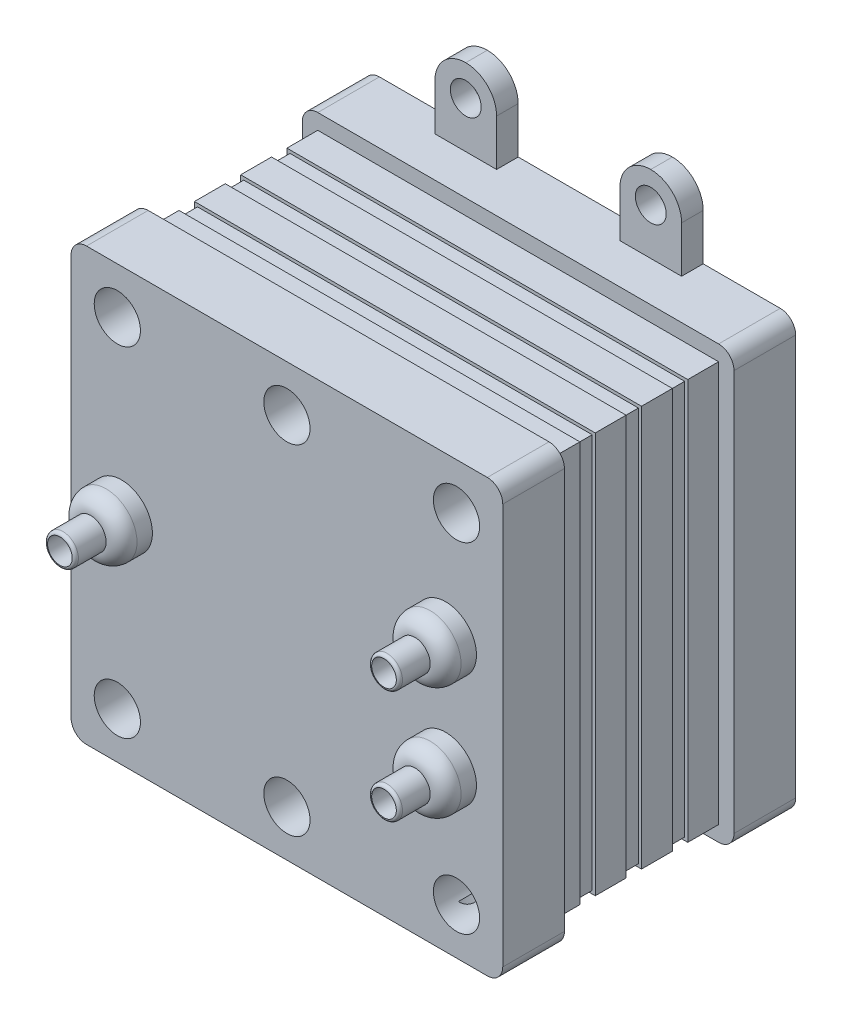
SolidWorks part; units mm, degrees
ref_plane "Plan de face" through (0, 0, 0) normal (0, 0, 1) x (1, 0, 0)
ref_plane "Plan de dessus" through (0, 0, 0) normal (0, 1, 0) x (1, 0, 0)
ref_plane "Plan de droite" through (0, 0, 0) normal (1, 0, 0) x (0, 0, -1)
sketch "Esquisse1" plane through (0, 0, 0) normal (0, 0, 1) x (1, 0, 0)
  line L1 (-74.4634, 41.4286) -> (55.5366, 41.4286)
  line L2 (-79.4634, 36.4286) -> (-79.4634, -93.5714)
  line L3 (-74.4634, -98.5714) -> (55.5366, -98.5714)
  line L4 (60.5366, 36.4286) -> (60.5366, -93.5714)
  arc A0 (-74.4634, 41.4286) -> (-79.4634, 36.4286) centre (-74.4634, 36.4286) ccw
  arc A1 (55.5366, 41.4286) -> (60.5366, 36.4286) centre (55.5366, 36.4286) cw
  arc A2 (55.5366, -98.5714) -> (60.5366, -93.5714) centre (55.5366, -93.5714) ccw
  arc A3 (-79.4634, -93.5714) -> (-74.4634, -98.5714) centre (-74.4634, -93.5714) ccw
  point P6 (-79.4634, 41.4286)
  point P9 (60.5366, 41.4286)
  point P14 (-79.4634, -98.5714)
  dimension "D3" = 5
  dimension "D1" = 140
  dimension "D2" = 140
extrude "Boss.-Extru.1" add sketch "Esquisse1" along normal blind 20
sketch "Esquisse2" plane through (0, 0, 20) normal (0, 0, 1) x (1, 0, 0)
  line L0 (-79.4634, 36.4286) -> (-79.4634, -93.5714) construction
  line L1 (-74.4634, 36.4286) -> (55.5366, 36.4286)
  line L2 (-74.4634, 36.4286) -> (-74.4634, -93.5714)
  line L3 (-74.4634, -93.5714) -> (55.5366, -93.5714)
  line L4 (55.5366, 36.4286) -> (55.5366, -93.5714)
  line L5 (60.5366, -93.5714) -> (60.5366, 36.4286) construction
  line L6 (-74.4634, -98.5714) -> (55.5366, -98.5714) construction
  line L7 (55.5366, 41.4286) -> (-74.4634, 41.4286) construction
  dimension "D1" = 5
  dimension "D2" = 5
  dimension "D3" = 5
  dimension "D4" = 5
extrude "Boss.-Extru.2" add sketch "Esquisse2" along normal blind 10
sketch "Esquisse4" plane through (0, 0, 30) normal (0, 0, 1) x (1, 0, 0)
  line L0 (55.5366, 36.4286) -> (-74.4634, 36.4286) construction
  line L1 (-73.4634, 35.4286) -> (54.5366, 35.4286)
  line L2 (-73.4634, 35.4286) -> (-73.4634, -92.5714)
  line L3 (-73.4634, -92.5714) -> (54.5366, -92.5714)
  line L4 (54.5366, 35.4286) -> (54.5366, -92.5714)
  line L5 (-74.4634, -93.5714) -> (55.5366, -93.5714) construction
  line L6 (-74.4634, 36.4286) -> (-74.4634, -93.5714) construction
  line L7 (55.5366, -93.5714) -> (55.5366, 36.4286) construction
  dimension "D1" = 1
  dimension "D2" = 1
  dimension "D3" = 1
  dimension "D4" = 1
extrude "Boss.-Extru.4" add sketch "Esquisse4" along normal blind 5
sketch "Esquisse5" plane through (0, 0, 35) normal (0, 0, 1) x (1, 0, 0)
  line L1 (-74.4634, 36.4286) -> (55.5366, 36.4286)
  line L2 (-74.4634, 36.4286) -> (-74.4634, -93.5714)
  line L3 (-74.4634, -93.5714) -> (55.5366, -93.5714)
  line L4 (55.5366, 36.4286) -> (55.5366, -93.5714)
extrude "Boss.-Extru.5" add sketch "Esquisse5" along normal blind 10
sketch "Esquisse6" plane through (0, 0, 45) normal (0, 0, 1) x (1, 0, 0)
  line L0 (-74.4634, 36.4286) -> (-74.4634, -93.5714) construction
  line L1 (-73.4634, 35.4286) -> (54.5366, 35.4286)
  line L2 (-73.4634, 35.4286) -> (-73.4634, -92.5714)
  line L3 (-73.4634, -92.5714) -> (54.5366, -92.5714)
  line L4 (54.5366, 35.4286) -> (54.5366, -92.5714)
  line L5 (55.5366, 36.4286) -> (-74.4634, 36.4286) construction
  line L6 (-74.4634, -93.5714) -> (55.5366, -93.5714) construction
  line L7 (55.5366, -93.5714) -> (55.5366, 36.4286) construction
  dimension "D1" = 1
  dimension "D2" = 1
  dimension "D3" = 1
  dimension "D4" = 1
extrude "Boss.-Extru.6" add sketch "Esquisse6" along normal blind 5
sketch "Esquisse7" plane through (0, 0, 50) normal (0, 0, 1) x (1, 0, 0)
  line L1 (-74.4634, 36.4286) -> (55.5366, 36.4286)
  line L2 (-74.4634, 36.4286) -> (-74.4634, -93.5714)
  line L3 (-74.4634, -93.5714) -> (55.5366, -93.5714)
  line L4 (55.5366, 36.4286) -> (55.5366, -93.5714)
extrude "Boss.-Extru.7" add sketch "Esquisse7" along normal blind 10
sketch "Esquisse8" plane through (0, 0, 60) normal (0, 0, 1) x (1, 0, 0)
  line L0 (-74.4634, 36.4286) -> (-74.4634, -93.5714) construction
  line L1 (-73.4634, 35.4286) -> (54.5366, 35.4286)
  line L2 (-73.4634, 35.4286) -> (-73.4634, -92.5714)
  line L3 (-73.4634, -92.5714) -> (54.5366, -92.5714)
  line L4 (54.5366, 35.4286) -> (54.5366, -92.5714)
  line L5 (55.5366, 36.4286) -> (-74.4634, 36.4286) construction
  line L6 (55.5366, -93.5714) -> (55.5366, 36.4286) construction
  line L7 (-74.4634, -93.5714) -> (55.5366, -93.5714) construction
  dimension "D1" = 1
  dimension "D2" = 1
  dimension "D3" = 1
  dimension "D4" = 1
extrude "Boss.-Extru.8" add sketch "Esquisse8" along normal blind 5
sketch "Esquisse9" plane through (0, 0, 65) normal (0, 0, 1) x (1, 0, 0)
  line L1 (-74.4634, 36.4286) -> (55.5366, 36.4286)
  line L2 (-74.4634, 36.4286) -> (-74.4634, -93.5714)
  line L3 (-74.4634, -93.5714) -> (55.5366, -93.5714)
  line L4 (55.5366, 36.4286) -> (55.5366, -93.5714)
extrude "Boss.-Extru.9" add sketch "Esquisse9" along normal blind 10
sketch "Esquisse10" plane through (0, 0, 75) normal (0, 0, 1) x (1, 0, 0)
  line L0 (-74.4634, -98.5714) -> (55.5366, -98.5714) construction
  line L1 (55.5366, -98.5714) -> (-74.4634, -98.5714)
  line L2 (60.5366, -93.5714) -> (60.5366, 36.4286)
  line L3 (55.5366, 41.4286) -> (-74.4634, 41.4286)
  line L4 (-79.4634, -93.5714) -> (-79.4634, 36.4286)
  line L5 (-79.4634, 36.4286) -> (-79.4634, -93.5714) construction
  arc A0 (-74.4634, -98.5714) -> (-79.4634, -93.5714) centre (-74.4634, -93.5714) cw
  arc A1 (55.5366, -98.5714) -> (60.5366, -93.5714) centre (55.5366, -93.5714) ccw
  arc A2 (60.5366, 36.4286) -> (55.5366, 41.4286) centre (55.5366, 36.4286) ccw
  arc A3 (-74.4634, 41.4286) -> (-79.4634, 36.4286) centre (-74.4634, 36.4286) ccw
  point P10 (-79.4634, -98.5714)
  point P13 (60.5366, -98.5714)
  point P18 (-79.4634, 41.4286)
  dimension "D3" = 5
  dimension "D1" = 140
  dimension "D2" = 140
extrude "Boss.-Extru.10" add sketch "Esquisse10" along normal blind 20
sketch "Esquisse11" plane through (0, 0, 0) normal (0, 0, -1) x (-1, 0, 0)
  line L0 (-60.5366, -93.5714) -> (-60.5366, 36.4286) construction
  line L1 (-55.5366, 41.4286) -> (74.4634, 41.4286) construction
  line L2 (79.4634, 36.4286) -> (79.4634, -93.5714) construction
  line L3 (74.4634, -98.5714) -> (-55.5366, -98.5714) construction
  circle A0 centre (-45.5366, 26.4286) radius 7.5
  circle A1 centre (9.4634, 26.4286) radius 7.5
  circle A2 centre (64.4634, 26.4286) radius 7.5
  circle A3 centre (64.4634, -83.5714) radius 7.5
  circle A4 centre (9.4634, -83.5714) radius 7.5
  circle A5 centre (-45.5366, -83.5714) radius 7.5
  dimension "D13" = 15
  dimension "D1" = 15
  dimension "D2" = 15
  dimension "D3" = 15
  dimension "D4" = 15
  dimension "D5" = 55
  dimension "D6" = 15
  dimension "D7" = 15
  dimension "D8" = 15
  dimension "D9" = 15
  dimension "D10" = 15
  dimension "D11" = 15
  dimension "D12" = 55
extrude "Enlèv. mat.-Extru.1" cut sketch "Esquisse11" against normal blind 110
sketch "Esquisse12" plane through (0, 0, 95) normal (0, 0, 1) x (1, 0, 0)
  circle A0 centre (42.0179, -10.2314) radius 10
  circle A1 centre (42.0179, -46.8914) radius 10
  circle A2 centre (-63.0897, -28.5714) radius 10
  circle A3 centre (45.5366, 26.4286) radius 7.5 construction
  circle A4 centre (45.5366, -83.5714) radius 7.5 construction
  circle A5 centre (-64.4634, 26.4286) radius 7.5 construction
  dimension "D5" = 20
  dimension "D1" = 36.66
  dimension "D2" = 36.66
  dimension "D3" = 36.68
  dimension "D4" = 55
extrude "Boss.-Extru.11" add sketch "Esquisse12" along normal blind 10
sketch "Esquisse13" plane through (0, 0, 105) normal (0, 0, 1) x (1, 0, 0)
  circle A0 centre (42.0179, -10.2314) radius 5
  circle A1 centre (42.0179, -46.8914) radius 5
  circle A2 centre (-63.0897, -28.5714) radius 5
  dimension "D1" = 10
  dimension "D2" = 10
  dimension "D3" = 10
extrude "Boss.-Extru.12" add sketch "Esquisse13" along normal blind 10
fillet "Congé2" radius 5 1 edges at (-53.0897, -28.5714, 105)
fillet "Congé3" radius 5 2 edges at (52.0179, -46.8914, 105) (52.0179, -10.2314, 105)
sketch "Esquisse14" plane through (0, 0, 115) normal (0, 0, 1) x (1, 0, 0)
  circle A0 centre (42.0179, -10.2314) radius 4
  circle A1 centre (42.0179, -46.8914) radius 4
  circle A2 centre (-63.0897, -28.5714) radius 4
  dimension "D1" = 8
  dimension "D2" = 8
  dimension "D3" = 8
extrude "Enlèv. mat.-Extru.2" cut sketch "Esquisse14" against normal blind 10
fillet "Congé4" radius 1 3 edges at (47.0179, -46.8914, 115) (47.0179, -10.2314, 115) (-58.0897, -28.5714, 115)
sketch "Esquisse15" plane through (0, -98.5714, 0) normal (0, -1, 0) x (1, 0, 0)
  circle A0 centre (-53.5135, 9.4224) radius 5
  circle A1 centre (36.4865, 9.4224) radius 5
  circle A2 centre (36.4865, 85.1887) radius 5
  circle A3 centre (-53.5135, 85.1887) radius 5
  dimension "D1" = 10
  dimension "D2" = 90
  dimension "D3" = 90
extrude "Enlèv. mat.-Extru.3" cut sketch "Esquisse15" against normal blind 10
sketch "Esquisse16" plane through (0, 41.4286, 0) normal (0, 1, 0) x (1, 0, 0)
  line L0 (55.5366, 0) -> (-74.4634, 0) construction
  line L1 (-49.4634, 0) -> (-29.4634, 0)
  line L2 (-49.4634, 0) -> (-49.4634, -7)
  line L3 (-49.4634, -7) -> (-29.4634, -7)
  line L4 (-29.4634, 0) -> (-29.4634, -7)
  line L5 (-74.4634, -20) -> (-74.4634, 0) construction
  line L6 (10.5366, 0) -> (30.5366, 0)
  line L7 (10.5366, 0) -> (10.5366, -7)
  line L8 (10.5366, -7) -> (30.5366, -7)
  line L9 (30.5366, 0) -> (30.5366, -7)
  line L10 (55.5366, -20) -> (55.5366, 0) construction
  dimension "D1" = 25
  dimension "D2" = 25
  dimension "D3" = 20
  dimension "D4" = 20
  dimension "D5" = 7
  dimension "D6" = 7
extrude "Boss.-Extru.13" add sketch "Esquisse16" along normal blind 25
fillet "Congé5" radius 10 4 edges at (-49.4634, 66.4286, 3.5) (-29.4634, 66.4286, 3.5) (10.5366, 66.4286, 3.5) (30.5366, 66.4286, 3.5)
sketch "Esquisse17" plane through (0, 0, 0) normal (0, 0, -1) x (-1, 0, 0)
  circle A0 centre (-20.5366, 56.4286) radius 5
  circle A1 centre (39.4634, 56.4286) radius 5
  dimension "D1" = 10
  dimension "D2" = 10
extrude "Enlèv. mat.-Extru.4" cut sketch "Esquisse17" against normal blind 25
sketch "Esquisse18" plane through (0, 41.4286, 0) normal (0, 1, 0) x (1, 0, 0)
  text T0 "+" font "Century Schoolbook" height 5
  text T1 "-" font "Century Schoolbook" height 5
